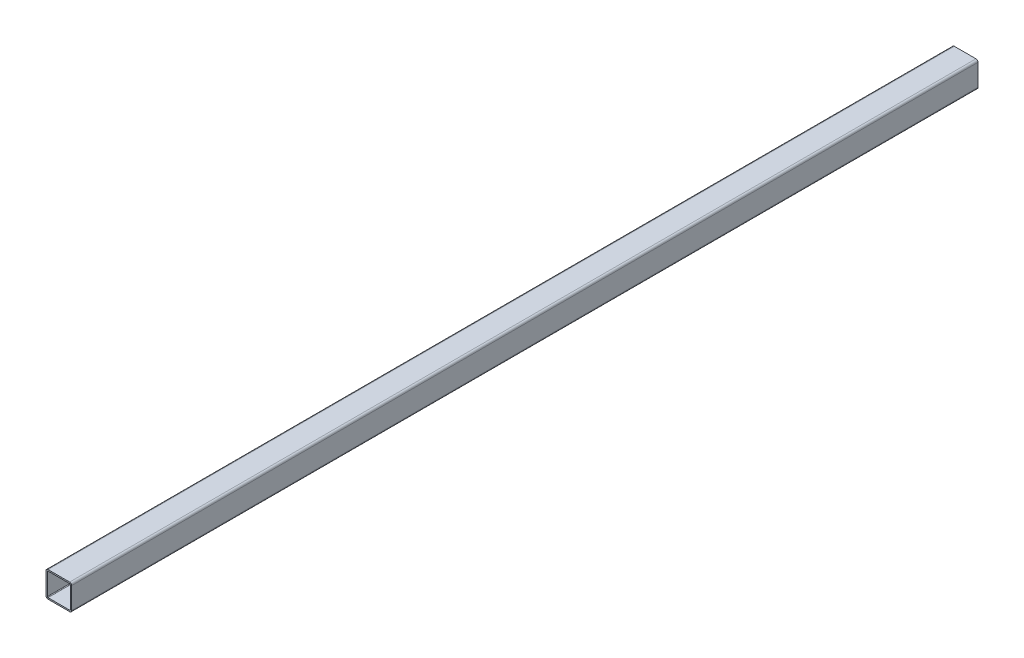
SolidWorks part; units mm, degrees
material "AISI 304"
ref_plane "Front Plane" through (0, 0, 0) normal (0, 0, 1) x (1, 0, 0)
ref_plane "Top Plane" through (0, 0, 0) normal (0, 1, 0) x (1, 0, 0)
ref_plane "Right Plane" through (0, 0, 0) normal (1, 0, 0) x (0, 0, -1)
sketch "Sketch1" plane through (0, 0, 0) normal (0, 0, 1) x (1, 0, 0)
  line L0 (-8, 8.5) -> (8, 8.5)
  line L1 (-8, -9.5) -> (8, -9.5)
  line L2 (-9.5, -8) -> (-9.5, 8)
  line L3 (-8, 9.5) -> (8, 9.5)
  line L4 (9.5, -8) -> (9.5, 8)
  line L5 (-9.5, -9.5) -> (9.5, 9.5) construction
  line L6 (-9.5, 9.5) -> (9.5, -9.5) construction
  line L7 (8.5, -8) -> (8.5, 8)
  line L8 (-8, -8.5) -> (8, -8.5)
  line L9 (-8.5, -8) -> (-8.5, 8)
  arc A0 (-8, -9.5) -> (-9.5, -8) centre (-8, -8) cw
  arc A1 (8, -9.5) -> (9.5, -8) centre (8, -8) ccw
  arc A2 (8, 9.5) -> (9.5, 8) centre (8, 8) cw
  arc A3 (-9.5, 8) -> (-8, 9.5) centre (-8, 8) cw
  arc A4 (8, 8.5) -> (8.5, 8) centre (8, 8) cw
  arc A5 (8, -8.5) -> (8.5, -8) centre (8, -8) ccw
  arc A6 (-8, -8.5) -> (-8.5, -8) centre (-8, -8) cw
  arc A7 (-8.5, 8) -> (-8, 8.5) centre (-8, 8) cw
  point P0 (0, 0)
  dimension "D2" = 1.5
  dimension "D3" = 1
  dimension "D1" = 19
extrude "Boss-Extrude1" add sketch "Sketch1" along normal blind 670
ref_axis "Axis1" through (0, 0, 0) along (0, 0, 1)
ref_plane "Plane1" through (0, 0, 0) normal (0.7071, -0.7071, 0) x (0, 0, -1)
